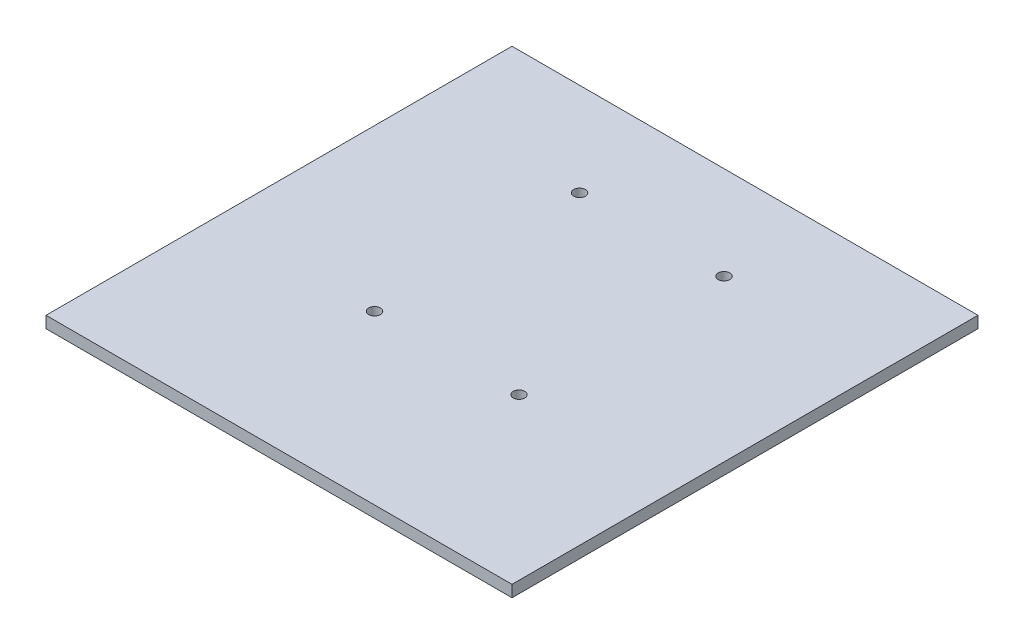
SolidWorks part; units mm, degrees
material "Corrugated Paper"
ref_plane "Front Plane" through (0, 0, 0) normal (0, 0, 1) x (1, 0, 0)
ref_plane "Top Plane" through (0, 0, 0) normal (0, 1, 0) x (1, 0, 0)
ref_plane "Right Plane" through (0, 0, 0) normal (1, 0, 0) x (0, 0, -1)
sketch "Sketch1" plane through (0, 0, 0) normal (0, 1, 0) x (1, 0, 0)
  line L0 (43.815, 0) -> (43.815, 127) construction
  line L1 (0, 0) -> (127, 0)
  line L2 (0, 0) -> (0, 127)
  line L3 (0, 127) -> (127, 127)
  line L4 (127, 0) -> (127, 127)
  line L5 (83.185, 127) -> (83.185, 0) construction
  line L6 (0, 45.72) -> (127, 45.72) construction
  line L7 (0, 101.6) -> (127, 101.6) construction
  line L8 (63.5, 127) -> (63.5, 0) construction
  line L9 (43.815, 20.2473) -> (83.185, 20.2473) construction
  line L10 (0, 63.5) -> (127, 63.5) construction
  circle A0 centre (43.815, 101.6) radius 1.5875
  circle A1 centre (83.185, 101.6) radius 1.5875
  circle A2 centre (43.815, 45.72) radius 1.5875
  circle A3 centre (83.185, 45.72) radius 1.5875
  point P25 (63.5, 20.2473)
  dimension "D7" = 3.175
  dimension "D8" = 3.175
  dimension "D9" = 3.175
  dimension "D10" = 3.175
  dimension "D1" = 127
  dimension "D2" = 127
  dimension "D3" = 39.37
  dimension "D4" = 55.88
  dimension "D5" = 17.78
extrude "Boss-Extrude1" add sketch "Sketch1" along normal blind 3.175
sketch "Sketch2" plane through (0, 3.175, 0) normal (0, 1, 0) x (1, 0, 0)
  line L0 (63.5, 127) -> (63.5, 0) construction
  line L1 (127, 127) -> (0, 127) construction
  line L2 (0, 0) -> (127, 0) construction
  line L3 (0, 63.5) -> (127, 63.5) construction
  line L4 (0, 127) -> (0, 0) construction
  line L5 (127, 0) -> (127, 127) construction
